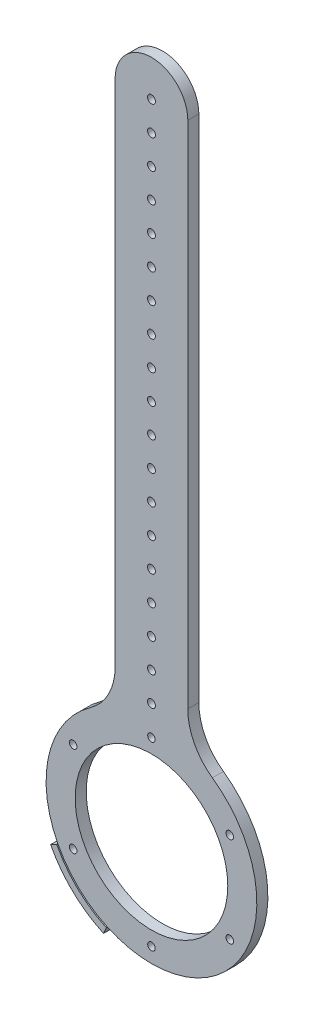
SolidWorks part; units mm, degrees
note: '?' marks a value the reader was unsure of.
material "Plain Carbon Steel"
ref_plane "Front Plane" through (0, 0, 0) normal (0, 0, 1) x (1, 0, 0)
ref_plane "Top Plane" through (0, 0, 0) normal (0, 1, 0) x (1, 0, 0)
ref_plane "Right Plane" through (0, 0, 0) normal (1, 0, 0) x (0, 0, -1)
sketch "Sketch1" plane through (0, 0, 0) normal (0, 0, 1) x (1, 0, 0)
  line L0 (0, 0) -> (0, 342.9) construction
  line L1 (15.875, 89.2513) -> (15.875, 327.025)
  line L4 (-15.875, 327.025) -> (-15.875, 89.2513)
  arc A1 (-15.875, 327.025) -> (15.875, 327.025) centre (0, 327.025) cw
  arc A2 (-15.875, 89.2513) -> (15.875, 89.2513) centre (0, 46.0375) ccw
  dimension "D1" = 342.9
  dimension "D4" = 92.075
  dimension "D2" = 15.875
  dimension "D3" = 15.875
extrude "Boss-Extrude1" add sketch "Sketch1" along normal blind 4.826
sketch "Sketch2" plane through (0, 0, 4.826) normal (0, 0, 1) x (1, 0, 0)
  circle A0 centre (0, 46.0375) radius 33.3375
  dimension "D1" = 66.675
extrude "Cut-Extrude1" cut sketch "Sketch2" against normal through all
fillet "Fillet1" radius 25.4 2 edges at (15.875, 89.2513, 2.413) (-15.875, 89.2513, 2.413)
hole_wizard "#8-32 Tapped Hole1" positions "Sketch3" profile "Sketch4" tap size "#8-32" standard "ANSI Inch"
sketch "Sketch3" plane through (0, 0, 4.826) normal (0, 0, 1) x (1, 0, 0)
  point P0 (0, 327.025)
  point P3 (0, 327.025)
sketch "Sketch4" plane through (0, 327.025, 4.826) normal (1, 0, 0) x (0, -1, 0)
  line L0 (0, 0) -> (0, 11.7058)
  line L1 (0, 11.7058) -> (1.7272, 10.668)
  line L2 (1.7272, 10.668) -> (1.7272, 0)
  line L5 (1.7272, 0) -> (0, 0)
  line L10 (0, 11.7058) -> (-1.7272, 10.668) construction
  line L11 (0, -6.35) -> (0, 107.95) construction
  dimension "Tap Drill Dia." = 3.4544
  dimension "Tap Drill Depth" = 10.668
  dimension "Drill Angle" = 118
cosmetic thread "Hole Thread1" parameters "D1"=4.826, "D2"=4.1656
cosmetic thread "Hole Thread3" parameters "D1"=4.826, "D2"=4.1656
pattern_linear "LPattern2" count 19 spacing 12.7 along (0, -1, 0) of "#8-32 Tapped Hole1"
ref_plane "Plane1" through (0, 233.5045, 0) normal (0, 1, 0) x (1, 0, 0)
ref_axis "Axis2" through (0, 46.0375, 4.826) along (0, 0, -1)?
sketch "Sketch7" plane through (0, 0, 0) normal (0, 0, -1) x (-1, 0, 0)
  circle A2 centre (0, 46.0375) radius 39.5
  dimension "D1" = 79
hole_wizard "CSK for M3 Flat Head Machine Screw1" positions "Sketch9" profile "Sketch8" countersink size "M3" standard "ANSI Metric" end condition through all
sketch "Sketch9" plane through (0, 0, 0) normal (0, 0, -1) x (-1, 0, 0)
  circle A0 centre (0, 46.0375) radius 39.5 construction
  point P0 (0, 85.5375)
sketch "Sketch8" plane through (0, 85.5375, 0) normal (1, 0, 0) x (0, 1, 0)
  line L0 (0, 0) -> (0, 4.826)
  line L1 (0, 4.826) -> (1.65, 4.826)
  line L2 (1.65, 4.826) -> (1.65, 1.525)
  line L3 (1.65, 1.525) -> (3.175, 0)
  line L5 (3.175, 0) -> (0, 0)
  line L6 (-1.65, 1.525) -> (-3.175, 0) construction
  line L11 (0, -6.35) -> (0, 107.95) construction
  dimension "Thru Hole Dia." = 3.3
  dimension "Thru Hole Depth" = 4.826
  dimension "Near C'Sink Dia." = 6.35
  dimension "Near C'Sink Angle" = 90
pattern_circular "CirPattern1" count 6 over 360 about axis through (0, 46.0375, 0) along (0, 0, 1) of "CSK for M3 Flat Head Machine Screw1"
sketch "Sketch10" plane through (0, 0, 0) normal (0, 0, -1) x (-1, 0, 0)
  line L0 (0, 46.0375) -> (39.8696, 23.0188) construction
  line L1 (34.208, 26.2875) -> (35.7955, 29.0371) construction
  line L2 (0, 46.0375) -> (40.8985, 24.9007) construction
  line L3 (40.8985, 24.9007) -> (19.193, 4.1916)
  line L4 (40.8985, 24.9007) -> (43.5636, 23.5234)
  line L5 (30.0457, 14.5461) -> (33.8508, 10.558) construction
  line L6 (19.193, 4.1916) -> (20.4437, 1.4647)
  line L7 (0, 46.0375) -> (19.193, 4.1916) construction
  arc A0 (19.193, 4.1916) -> (40.8985, 24.9007) centre (0, 46.0375) ccw
  arc A1 (43.5636, 23.5234) -> (20.4437, 1.4647) centre (0, 46.0375) cw
  circle A2 centre (34.208, 26.2875) radius 1.65 construction
  circle A3 centre (34.208, 26.2875) radius 3.175 construction
  circle A4 centre (0, 46.0375) radius 33.3375 construction
  arc A5 (-26.5994, 83.613) -> (26.5994, 83.613) centre (0, 46.0375) ccw construction
  point P6 (35.0018, 27.6623)
  point P20 (31.7799, 12.7285)
  arc M42 (-26.5994, 83.613) -> (26.5994, 83.613) centre (0, 46.0375) ccw
  dimension "D1" = 0.254
  dimension "D2" = 30
  dimension "D3" = 3
  dimension "D4" = 3
  dimension "D5" = 3
extrude "Boss-Extrude2" add sketch "Sketch10" along normal blind 7 and the other way blind 5.326 contours A1 L4 L6 M42 | A0
sketch "Sketch11" plane through (0, 0, 0) normal (0, 0, -1) x (-1, 0, 0)
  line L0 (40.8985, 24.9007) -> (39.1218, 25.819)
  line L1 (19.193, 4.1916) -> (18.3592, 6.0095)
  line L2 (19.193, 4.1916) -> (20.4437, 1.4647) construction
  line L3 (40.8985, 24.9007) -> (43.5636, 23.5234) construction
  line L4 (31.7799, 12.7285) -> (-31.78, 79.3466) construction
  line L5 (0, 46.0375) -> (31.7799, 12.7285) construction
  arc A0 (18.3592, 6.0095) -> (39.1218, 25.819) centre (0, 46.0375) ccw
  arc A1 (19.193, 4.1916) -> (40.8985, 24.9007) centre (0, 46.0375) ccw construction
  circle A4 centre (0, 46.0375) radius 33.3375 construction
  point P16 (30.3993, 14.1756)
  dimension "D1" = 2
  dimension "D2" = 2
  dimension "D3" = 2
ref_plane "Plane2" through (-17.4455, 8.0015, 0) normal (0.909, -0.4169, 0) x (0, 0, -1)
sketch "Sketch12" plane through (-17.4455, 8.0015, 0) normal (0.909, -0.4169, 0) x (0, 0, -1)
  line L0 (0, -4.1916) -> (3.5, -4.1916)
  line L1 (0, -4.1916) -> (7, -4.1916) construction
  line L2 (0, -4.1916) -> (0, -2.1916)
  line L3 (0, 70.884) -> (0, 77.234) construction
  arc A0 (0, -2.1916) -> (3.5, -4.1916) centre (3.5, -0.1291) ccw
  dimension "D1" = 2
sweep "Sweep2" add profiles "Sketch12" path edge at (-31.7799, 12.7285, 0)
ref_plane "Plane3" through (-75, 0, 0) normal (1, 0, 0) x (0, 0, -1)
